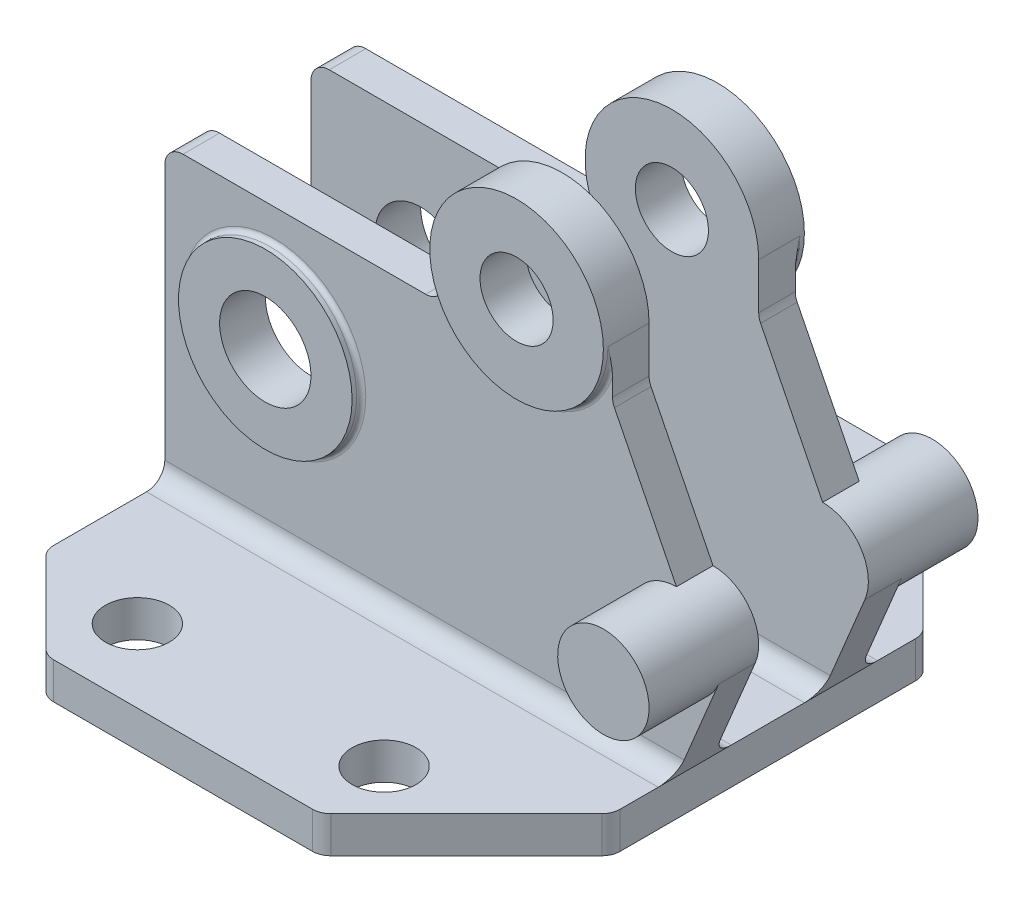
SolidWorks part; units mm, degrees
material "Cast Carbon Steel"
ref_plane "Front Plane" through (0, 0, 0) normal (0, 0, 1) x (1, 0, 0)
ref_plane "Top Plane" through (0, 0, 0) normal (0, 1, 0) x (1, 0, 0)
ref_plane "Right Plane" through (0, 0, 0) normal (1, 0, 0) x (0, 0, -1)
sketch "Sketch1" plane through (0, 0, 0) normal (0, 1, 0) x (1, 0, 0)
  line L0 (-28, 23) -> (-18, 33)
  line L5 (-18, -33) -> (12, -33)
  line L6 (-28, -23) -> (-28, 23)
  line L7 (-18, 33) -> (12, 33)
  line L8 (28, -17) -> (28, 17)
  line L9 (-28, -33) -> (28, 33) construction
  line L10 (-28, 33) -> (28, -33) construction
  line L11 (-28, -23) -> (-18, -33)
  line L12 (12, 33) -> (28, 17)
  line L13 (12, -33) -> (28, -17)
  point P0 (0, 0)
  dimension "D1" = 56
  dimension "D2" = 66
extrude "Boss-Extrude1" add sketch "Sketch1" along normal blind 4
ref_plane "Plane1" through (0, 0, 0) normal (0, 0, 1) x (1, 0, 0)
ref_plane "Plane2" through (0, 0, 6) normal (0, 0, 1) x (1, 0, 0)
sketch "Sketch3" plane through (0, 0, 6) normal (0, 0, 1) x (1, 0, 0)
  line L1 (-28, 4) -> (28, 4)
  line L2 (-28, 4) -> (-28, 36)
  line L3 (-28, 36) -> (3.754, 36)
  line L5 (21, 41.5) -> (21, 36)
  line L6 (21, 36) -> (28, 22)
  line L7 (28, 4) -> (32.6154, 15.0769)
  circle A0 centre (11.5, 41.5) radius 9.5
  circle A1 centre (11.5, 41.5) radius 4
  circle A2 centre (28, 17) radius 5
  circle A3 centre (-16, 23) radius 9.5
  circle A4 centre (-16, 23) radius 5
  point P8 (0, 0)
  point P19 (0, 0)
  point P20 (3.754, 36)
  dimension "D2" = 19
  dimension "D3" = 8
  dimension "D6" = 13
  dimension "D7" = 10
  dimension "D8" = 19
  dimension "D9" = 10
  dimension "D11" = 12
  dimension "D1" = 32
  dimension "D4" = 39.5
  dimension "D5" = 37.5
  dimension "D10" = 19
extrude "Boss-Extrude2" add sketch "Sketch3" along normal blind 4 contours A2 L6 L3 A0 L2 L1 A3 | A3 A4 | L3 A0 | A0 L3 A1 | A2 | A2 region at (1.6308, 18.5555, 6) region at (28, 17, 6) region at (8.6952, 50.2949, 6) region at (-25.2313, 23, 6)
extrude "Boss-Extrude3" add sketch "Sketch3<5>" along normal blind 5 contours A3 A4 | A0 A1 | A0 region at (8.6952, 50.2949, 6) region at (-25.2313, 23, 6)
sketch "Sketch3<5>" plane through (0, 0, 6) normal (0, 0, 1) x (1, 0, 0) same geometry as "Sketch3"
extrude "Boss-Extrude4" add sketch "Sketch3<6>" along normal blind 12 contours A2 | A2 region at (28, 17, 6)
sketch "Sketch3<6>" plane through (0, 0, 6) normal (0, 0, 1) x (1, 0, 0) same geometry as "Sketch3"
mirror "Mirror1" about plane through (0, 0, 0) normal (0, 0, 1) of "Boss-Extrude4", "Boss-Extrude3", "Boss-Extrude2"
sketch "Sketch4" plane through (0, 4, 0) normal (0, 1, 0) x (1, 0, 0)
  line L1 (12, 33) -> (-18, 33) construction
  line L2 (-28, 23) -> (-28, 10) construction
  circle A0 centre (-16, 25) radius 3.5
  circle A1 centre (11, 25) radius 3.5
  point P8 (0, 0)
  dimension "D1" = 7
  dimension "D4" = 27
  dimension "D2" = 8
  dimension "D5" = 12
extrude "Cut-Extrude2" cut sketch "Sketch4" against normal through all
mirror "Mirror2" about plane through (0, 0, 0) normal (0, 0, 1) of "Cut-Extrude2"
fillet "Fillet1" radius 2 8 edges at (-28, 2, 23) (-18, 2, 33) (12, 2, -33) (-18, 2, -33) (-28, 2, -23) (28, 2, -17) (28, 2, 17) (12, 2, 33)
fillet "Fillet2" radius 2 4 edges at (-28, 36, -8) (-28, 36, 8) (3.754, 36, -8) (3.754, 36, 8)
fillet "Fillet3" radius 0.5 4 edges at (12.9631, 32.1133, 10) (12.9631, 32.1133, -10) (-25.5, 23, -10) (-6.5, 23, 10)
fillet "Fillet4" radius 2 4 edges at (0, 4, -6) (0, 4, -10) (0, 4, 6) (0, 4, 10)
fillet "Fillet5" radius 2 2 edges at (21, 36, 8) (21, 36, -8)
equation "\"A\"= 66"
equation "\"B\"= 56"
equation "\"D1@Sketch1\"=\"B\""
equation "\"D2@Sketch1\"=\"A\""
